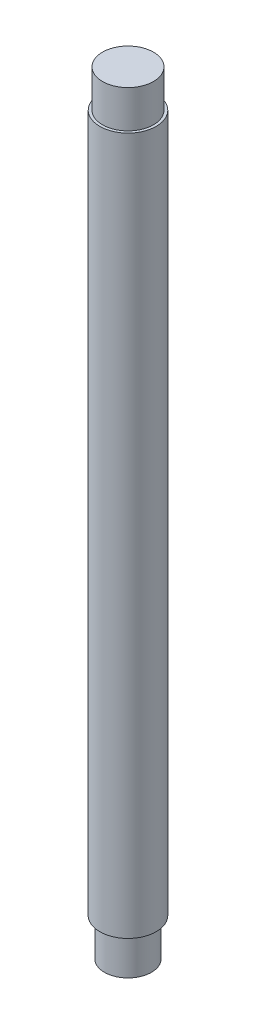
SolidWorks part; units mm, degrees
ref_plane "Front Plane" through (0, 0, 0) normal (0, 0, 1) x (1, 0, 0)
ref_plane "Top Plane" through (0, 0, 0) normal (0, 1, 0) x (1, 0, 0)
ref_plane "Right Plane" through (0, 0, 0) normal (1, 0, 0) x (0, 0, -1)
sketch "Sketch2" plane through (0, 0, 0) normal (0, 1, 0) x (1, 0, 0)
  circle A0 centre (0, 0) radius 9.525
  dimension "D1" = 19.05
extrude "Boss-Extrude1" add sketch "Sketch2" along normal blind 236
sketch "Sketch3" plane through (0, 236, 0) normal (0, 1, 0) x (1, 0, 0)
  circle A0 centre (0, 0) radius 8.621
extrude "Boss-Extrude2" add sketch "Sketch3" along normal blind 12.7
sketch "Sketch4" plane through (0, 0, 0) normal (0, -1, 0) x (1, 0, 0)
  circle A0 centre (0, 0) radius 7.9375
  dimension "D1" = 15.875
extrude "Boss-Extrude3" add sketch "Sketch4" along normal blind 12.7
